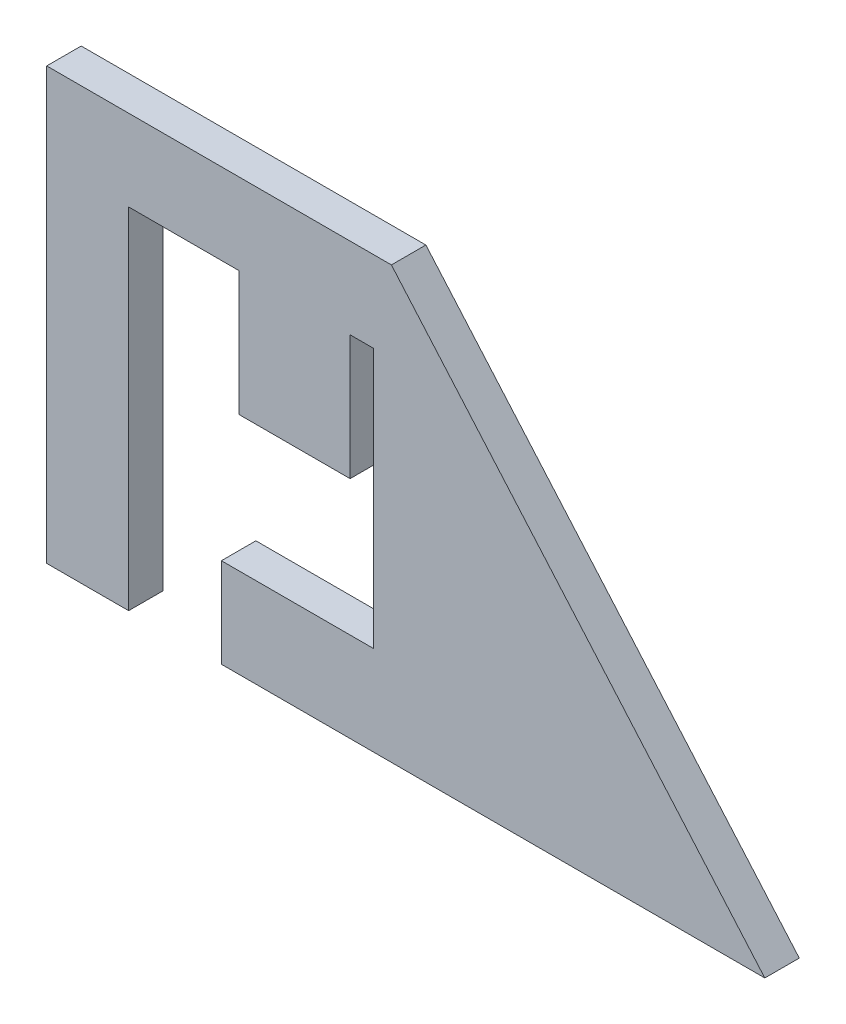
SolidWorks part; units mm, degrees
ref_plane "Plan de face" through (0, 0, 0) normal (0, 0, 1) x (1, 0, 0)
ref_plane "Plan de dessus" through (0, 0, 0) normal (0, 1, 0) x (1, 0, 0)
ref_plane "Plan de droite" through (0, 0, 0) normal (1, 0, 0) x (0, 0, -1)
sketch "Esquisse1" plane through (0, 0, 0) normal (0, 0, 1) x (1, 0, 0)
  line L0 (0, 0) -> (250, 0)
  line L1 (250, 0) -> (120, 150)
  line L2 (120, 150) -> (0, 150)
  line L3 (0, 150) -> (0, 0)
  dimension "D1" = 250
  dimension "D2" = 150
  dimension "D3" = 120
extrude "Boss.-Extru.1" add sketch "Esquisse1" against normal blind 6 and the other way blind 6
sketch "Esquisse2" plane through (0, 0, 6) normal (0, 0, 1) x (1, 0, 0)
  line L0 (0, 0) -> (250, 0) construction
  line L1 (113.7241, 0) -> (28.5158, 0) construction
  line L2 (113.7241, 0) -> (113.7241, 121.7427) construction
  line L3 (113.7241, 121.7427) -> (28.5158, 121.7427) construction
  line L4 (28.5158, 0) -> (28.5158, 121.7427)
  line L5 (0, 150) -> (0, 0) construction
  line L6 (113.7241, 31.2245) -> (60.8165, 31.2245)
  line L7 (60.8165, 31.2245) -> (60.8165, 0)
  line L8 (60.8165, 0) -> (28.5158, 0)
  line L9 (28.5158, 121.7427) -> (67.0124, 121.7427)
  line L10 (67.0124, 121.7427) -> (67.0124, 78.3647)
  line L11 (67.0124, 78.3647) -> (105.6233, 78.3647)
  line L12 (105.6233, 78.3647) -> (105.6233, 121.7427)
  line L13 (105.6233, 121.7427) -> (113.7241, 121.7427)
  line L14 (113.7241, 121.7427) -> (113.7241, 31.2245)
  dimension "D1" = 28.5158
  dimension "D2" = 113.7241
  dimension "D3" = 121.7427
  dimension "D4" = 60.8165
  dimension "D5" = 67.0124
  dimension "D6" = 105.6233
  dimension "D7" = 31.2245
  dimension "D8" = 78.3647
extrude "Enlèv. mat.-Extru.1" cut sketch "Esquisse2" against normal through all
